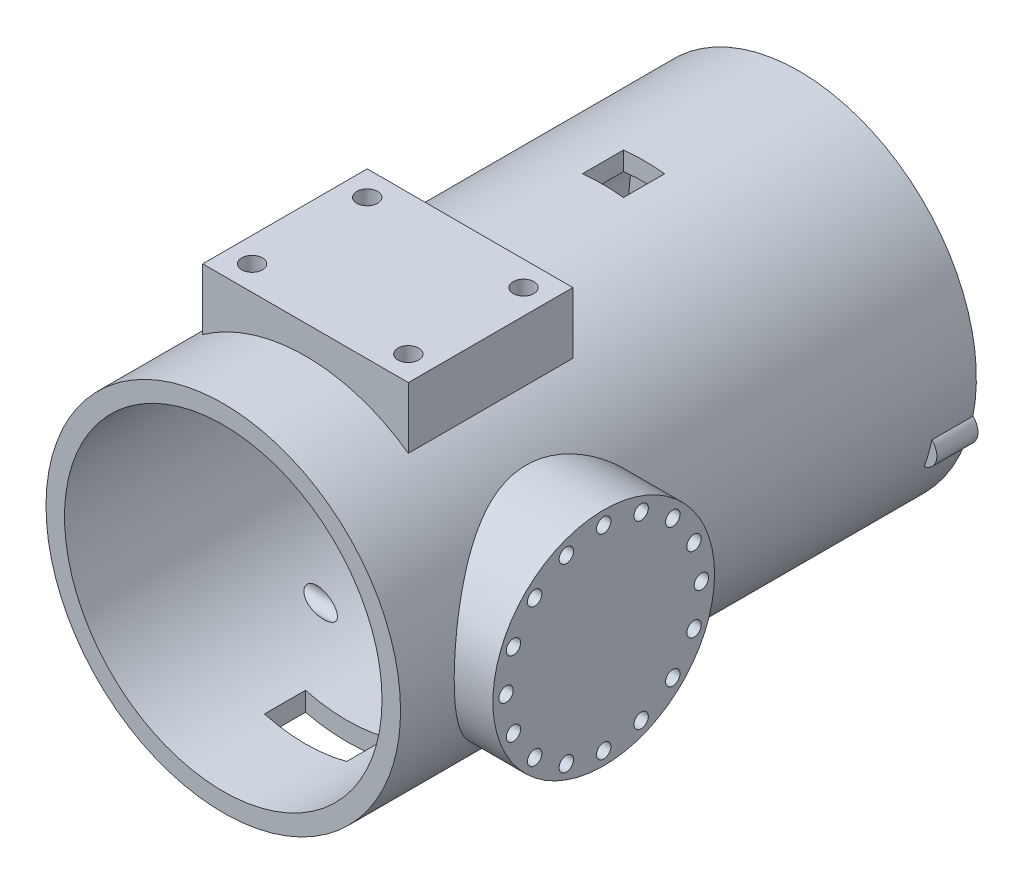
SolidWorks part; units mm, degrees
other "Markup1"
sketch "Sketch14" plane through (-43.1, 43.1, 140) normal (-0.1765, 0.0048, 0.9843) x (0.9842, -0.0149, 0.1765)
other "Markup2"
sketch "Sketch23" plane through (45.1, -43.1, 140) normal (0.9491, -0.0629, 0.3087) x (0.311, 0.031, -0.9499)
ref_plane "Front Plane" through (0, 0, 0) normal (0, 0, 1) x (1, 0, 0)
ref_plane "Top Plane" through (0, 0, 0) normal (0, 1, 0) x (1, 0, 0)
ref_plane "Right Plane" through (0, 0, 0) normal (1, 0, 0) x (0, 0, -1)
sketch "Sketch1" plane through (0, 0, 0) normal (0, 0, 1) x (1, 0, 0)
  circle A1 centre (0, 0) radius 43.1
  dimension "D1" = 86.2
extrude "Main Body" add sketch "Sketch1" along normal blind 140
ref_plane "Plane1" through (0, 43.1, 0) normal (0, 1, 0) x (1, 0, 0)
sketch "Sketch34" [suppressed] plane through (0, 43.1, 0) normal (0, 1, 0) x (1, 0, 0)
  line L6 (-5, -13) -> (5, -13)
  line L8 (-5, -13) -> (-5, -3)
  line L9 (-5, -3) -> (5, -3)
  line L10 (5, -13) -> (5, -3)
  line L11 (-5, -13) -> (5, -3) construction
  line L12 (-5, -3) -> (5, -13) construction
  point P0 (0, -8)
  dimension "D1" = 8
  dimension "D2" = 10
  dimension "D3" = 10
sketch "Sketch6" plane through (0, 43.1, 0) normal (0, 1, 0) x (1, 0, 0)
  line L2 (-5, -47.7) -> (5, -47.7)
  line L3 (-5, -47.7) -> (-5, -37.7)
  line L4 (-5, -37.7) -> (5, -37.7)
  line L5 (5, -47.7) -> (5, -37.7)
  line L6 (-5, -47.7) -> (5, -37.7) construction
  line L7 (-5, -37.7) -> (5, -47.7) construction
  point P2 (0, -42.7)
  dimension "D2" = 10
  dimension "D1" = 42.7
  dimension "D3" = 10
extrude "Cut-Extrude3" cut sketch "Sketch6" against normal through all
ref_plane "Plane2" through (52.5, 0, 0) normal (1, 0, 0) x (0, 0, -1)
sketch "Sketch8" plane through (52.5, 0, 0) normal (1, 0, 0) x (0, 0, -1)
  circle A0 centre (-100, 0) radius 26.95
  dimension "D1" = 53.9
  dimension "D2" = 100
extrude "Boss-Extrude2" add sketch "Sketch8" against normal blind 20
mirror "Mirror1" [suppressed] about plane through (0, 0, 0) normal (1, 0, 0)
ref_plane "Plane3" through (0, 50, 0) normal (0, 1, 0) x (1, 0, 0)
sketch "Sketch33" plane through (0, 50, 0) normal (0, 1, 0) x (1, 0, 0)
  line L1 (-25, -120) -> (25, -120)
  line L2 (-25, -120) -> (-25, -80)
  line L3 (-25, -80) -> (25, -80)
  line L4 (25, -120) -> (25, -80)
  line L5 (-25, -120) -> (25, -80) construction
  line L6 (-25, -80) -> (25, -120) construction
  point P0 (0, -100)
  dimension "D1" = 100
  dimension "D2" = 40
  dimension "D3" = 50
extrude "Boss-Extrude11" add sketch "Sketch33" against normal blind 22
sketch "Sketch35" plane through (0, 50, 0) normal (0, 1, 0) x (1, 0, 0)
  line L0 (-25, -120) -> (-25, -80) construction
  line L1 (25, -120) -> (25, -80) construction
  line L2 (25, -80) -> (-25, -80) construction
  line L3 (-25, -120) -> (25, -120) construction
  circle A0 centre (-19, -86) radius 2.525
  circle A1 centre (19, -86) radius 2.525
  circle A2 centre (-19, -114) radius 2.525
  circle A3 centre (19, -114) radius 2.525
  dimension "D1" = 5.05
  dimension "D2" = 6
  dimension "D3" = 6
  dimension "D4" = 6
  dimension "D5" = 6
extrude "Cut-Extrude14" cut sketch "Sketch35" against normal blind 4
sketch "Sketch5" plane through (0, 0, 140) normal (0, 0, 1) x (1, 0, 0)
  circle A0 centre (0, 0) radius 32
  dimension "D1" = 64
extrude "Hole 1" cut sketch "Sketch5" against normal through all
sketch "Sketch10" plane through (0, 0, 0) normal (0, 1, 0) x (1, 0, 0)
  line L0 (43.1, 0) -> (-43.1, 0) construction
  line L1 (-10, -120) -> (10, -120)
  line L2 (-10, -120) -> (-10, -110)
  line L3 (-10, -110) -> (10, -110)
  line L4 (10, -120) -> (10, -110)
  line L5 (-10, -120) -> (10, -110) construction
  line L6 (-10, -110) -> (10, -120) construction
  point P0 (0, -115)
  point P7 (-10, -115)
  dimension "D1" = 110
  dimension "D2" = 10
  dimension "D3" = 20
extrude "Motor Wire Hole" cut sketch "Sketch10" against normal through all
sketch "Sketch27" plane through (0, 0, 0) normal (1, 0, 0) x (0, 0, -1)
  line L1 (-100, -36.5) -> (-60, -36.5)
  line L2 (-100, -36.5) -> (-100, -27.5)
  line L3 (-100, -27.5) -> (-60, -27.5)
  line L4 (-60, -36.5) -> (-60, -27.5)
  dimension "D1" = 60
  dimension "D2" = 27.5
  dimension "D3" = 40
  dimension "D4" = 9
extrude "Boss-Extrude9" add sketch "Sketch27" along normal blind 33 and the other way blind 33
sketch "Sketch11" plane through (0, 0, 0) normal (1, 0, 0) x (0, 0, -1)
  circle A0 centre (-65, -32) radius 2.25
  circle A1 centre (-95, -32) radius 2.25
  dimension "D3" = 4.5
  dimension "D1" = 65
  dimension "D2" = 32
  dimension "D4" = 30
extrude "Cut-Extrude6" cut sketch "Sketch11" against normal through all both and the other way through all
sketch "Sketch28" plane through (-33, 0, 0) normal (-1, 0, 0) x (0, 0, 1)
  line L0 (62.8927, -28.35) -> (67.1073, -28.35)
  line L1 (67.1073, -28.35) -> (69.2147, -32)
  line L2 (69.2147, -32) -> (67.1073, -35.65)
  line L3 (67.1073, -35.65) -> (62.8927, -35.65)
  line L4 (62.8927, -35.65) -> (60.7853, -32)
  line L6 (60.7853, -32) -> (62.8927, -28.35)
  line L7 (92.8927, -28.35) -> (97.1073, -28.35)
  line L8 (97.1073, -28.35) -> (99.2147, -32)
  line L9 (99.2147, -32) -> (97.1073, -35.65)
  line L10 (97.1073, -35.65) -> (92.8927, -35.65)
  line L11 (92.8927, -35.65) -> (90.7853, -32)
  line L12 (90.7853, -32) -> (92.8927, -28.35)
  circle A0 centre (65, -32) radius 3.65 construction
  circle A1 centre (65, -32) radius 2.25 construction
  circle A2 centre (95, -32) radius 3.65 construction
  circle A3 centre (95, -32) radius 2.25 construction
  dimension "D2" = 7.3
extrude "Cut-Extrude7" cut sketch "Sketch28" against normal blind 3
sketch "Sketch29" plane through (33, 0, 0) normal (1, 0, 0) x (0, 0, -1)
  circle A0 centre (-95, -32) radius 3.6
  circle A1 centre (-65, -32) radius 3.6
  dimension "D1" = 7.2
extrude "Cut-Extrude8" cut sketch "Sketch29" against normal blind 4
sketch "Sketch2" plane through (0, 0, 140) normal (0, 0, 1) x (1, 0, 0)
  circle A0 centre (0, 0) radius 38.6
  dimension "D1" = 77.2
extrude "Cut-Extrude5" cut sketch "Sketch2" against normal blind 135
sketch "Sketch9" plane through (0, 0, 5) normal (0, 0, 1) x (1, 0, 0)
  circle A0 centre (0, 0) radius 38.1
  circle A1 centre (0, 0) radius 36.44
  dimension "D1" = 76.2
  dimension "D2" = 1.66
extrude "Boss-Extrude3" add sketch "Sketch9" along normal blind 10
extrude "Cut-Extrude13" [suppressed] cut sketch "Sketch34" against normal blind 15
sketch "Sketch30" plane through (52.5, 0, 0) normal (1, 0, 0) x (0, 0, -1)
  line L0 (-100, 23.75) -> (-100, 0) construction
  circle A0 centre (-100, 0) radius 23.75 construction
  circle A1 centre (-100, 23.75) radius 1.75
  circle A2 centre (-90.9113, 21.9421) radius 1.75
  circle A3 centre (-83.2062, 16.7938) radius 1.75
  circle A4 centre (-78.0579, 9.0887) radius 1.75
  circle A5 centre (-76.25, 0) radius 1.75
  circle A6 centre (-78.0579, -9.0887) radius 1.75
  circle A7 centre (-83.2062, -16.7938) radius 1.75
  circle A8 centre (-90.9113, -21.9421) radius 1.75
  circle A9 centre (-100, -23.75) radius 1.75
  circle A10 centre (-109.0887, -21.9421) radius 1.75
  circle A11 centre (-116.7938, -16.7938) radius 1.75
  circle A12 centre (-121.9421, -9.0887) radius 1.75
  circle A13 centre (-123.75, 0) radius 1.75
  circle A14 centre (-121.9421, 9.0887) radius 1.75
  circle A15 centre (-116.7938, 16.7938) radius 1.75
  circle A16 centre (-109.0887, 21.9421) radius 1.75
  point P38 (-100, 0)
  dimension "D1" = 47.5
  dimension "D2" = 3.5
  dimension "D3" = 16
extrude "Cut-Extrude9" cut sketch "Sketch30" against normal up to surface (22.0714 mm away) up to face at (21.6187, -31.978, 97.2499)
sketch "Sketch31" plane through (52.5, 0, 0) normal (1, 0, 0) x (0, 0, -1)
  line L0 (0, -43.1) -> (0, 43.1) construction
  line L1 (0, -15) -> (-10, -15)
  line L2 (0, -15) -> (0, -7.5)
  line L3 (0, -7.5) -> (-10, -7.5)
  line L4 (-10, -15) -> (-10, -7.5)
  dimension "D1" = 15
  dimension "D2" = 7.5
  dimension "D3" = 10
extrude "Boss-Extrude10" add sketch "Sketch31" against normal up to body from offset 9 offset against normal yes
sketch "Sketch32" plane through (0, 0, 0) normal (0, 0, -1) x (-1, 0, 0)
  line L0 (-43.5, -11.25) -> (-29.9573, -11.25) construction
  line L1 (-43.5, -15) -> (-43.5, -7.5) construction
  line L3 (-42.4424, -7.5) -> (-43.5, -7.5) construction
  line L5 (-43.5, -15) -> (-43.5, -7.5)
  line L6 (-43.5, -7.5) -> (-42.4424, -7.5)
  circle A0 centre (0, 0) radius 32 construction
  arc A2 (-40.4056, -15) -> (-42.4424, -7.5) centre (0, 0) ccw construction
  arc A3 (-40.4056, -15) -> (-42.2658, -8.4385) centre (-39.6806, -11.25) cw
  arc A4 (-42.2658, -8.4385) -> (-42.4424, -7.5) centre (0, 0) cw
  line M3 (-42.4424, -7.5) -> (-43.5, -7.5)
  line M4 (-43.5, -7.5) -> (-43.5, -15)
  line M5 (-43.5, -15) -> (-40.4056, -15)
extrude "Cut-Extrude10" cut sketch "Sketch32" against normal up to surface (10 mm away) contours M4 M3 | L5 M5 region at (43.0347, -8.5479, 0) region at (42.7123, -14.1508, 0) up to face at (42.5043, -11.2615, 10)
